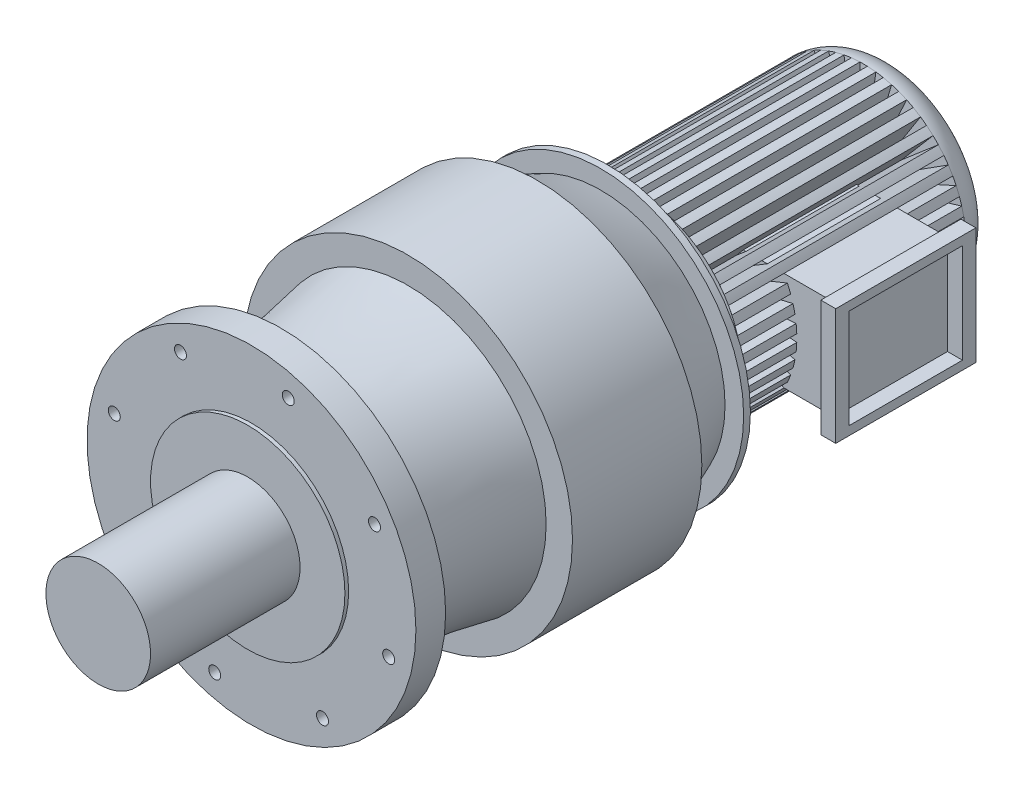
SolidWorks part; units mm, degrees
material "PBT Genel Kullanım"
ref_plane "Ön Düzlem" through (0, 0, 0) normal (0, 0, 1) x (1, 0, 0)
ref_plane "Üst Düzlem" through (0, 0, 0) normal (0, 1, 0) x (1, 0, 0)
ref_plane "Sağ Düzlem" through (0, 0, 0) normal (1, 0, 0) x (0, 0, -1)
sketch "Çizim1" plane through (0, 0, 0) normal (1, 0, 0) x (0, 0, -1)
  line L0 (0, 0) -> (0, 70)
  line L1 (0, 70) -> (200, 70)
  line L2 (200, 70) -> (200, 130)
  line L3 (244.7518, 220) -> (244.7518, 166.1344)
  line L4 (414.4471, 184.7501) -> (414.4471, 220)
  line L5 (200, 130) -> (205, 130)
  line L6 (205, 130) -> (205, 220)
  line L7 (205, 220) -> (244.7518, 220)
  line L8 (414.4471, 220) -> (459.3436, 220)
  line L9 (459.3436, 220) -> (587.4629, 220)
  line L10 (587.4629, 220) -> (587.4629, 203.9807)
  line L11 (0, 0) -> (1063.8815, 0) construction
  line L12 (672.3685, 166.1344) -> (672.3685, 191.0474)
  line L13 (672.3685, 191.0474) -> (681.4104, 191.0474)
  line L14 (681.4104, 118.9552) -> (723.8815, 118.9552)
  line L15 (723.8815, 118.9552) -> (723.8815, 136.4076)
  line L16 (681.4104, 191.0474) -> (681.4104, 118.9552)
  line L17 (723.8815, 136.4076) -> (1023.8815, 136.4076)
  line L18 (1063.8815, 96.4076) -> (1063.8815, 0)
  arc A0 (244.7518, 166.1344) -> (414.4471, 184.7501) centre (244.7518, 948.8914) ccw
  arc A1 (1063.8815, 96.4076) -> (1023.8815, 136.4076) centre (1023.8815, 96.4076) ccw
  arc A2 (587.4629, 203.9807) -> (672.3685, 166.1344) centre (948.0374, 898.7428) ccw
  dimension "D4" = 40
  dimension "D1" = 70
  dimension "D2" = 205
  dimension "D3" = 200
  dimension "D5" = 130
  dimension "D6" = 220
  dimension "D8" = 300
revolve "Döndür1" add sketch "Çizim1" angle 360 about L11 region at (0, 83.1407, -552.2359)
sketch "Çizim2" plane through (0, 0, -205) normal (0, 0, 1) x (1, 0, 0)
  line L0 (0, 0) -> (0, 243.7784) construction
  circle A1 centre (-95, 164.5448) radius 8
extrude "Kes-Ekstrüzyon4" cut sketch "Çizim2" against normal up to next contours A1 region at (-95, 164.5448, -205)
pattern_circular "Dairesel Çoğaltma1" count 8 over 360 of "Kes-Ekstrüzyon4"
ref_plane "Düzlem1" through (136.4076, 0, 0) normal (1, 0, 0) x (0, 0, -1)
sketch "Çizim4" plane through (136.4076, 0, 0) normal (1, 0, 0) x (0, 0, -1)
  line L1 (1023.8815, 136.4076) -> (1023.8815, -136.4076) construction
  line L2 (723.8815, 118.9552) -> (723.8815, -118.9552) construction
  line L3 (1023.8815, 0) -> (1023.8815, 5)
  line L4 (1023.8815, 5) -> (723.8815, 5)
  line L5 (723.8815, 5) -> (723.8815, 0)
  line L6 (1023.8815, -5) -> (723.8815, -5)
  line L7 (1023.8815, 0) -> (1023.8815, -5)
  line L8 (723.8815, 0) -> (723.8815, -5)
extrude "Kes-Ekstrüzyon5" cut sketch "Çizim4" against normal blind 80 draft 5
pattern_circular "Dairesel Çoğaltma2" count 40 over 360 of "Kes-Ekstrüzyon5"
sketch "Çizim5" plane through (136.4076, 0, 0) normal (1, 0, 0) x (0, 0, -1)
  line L0 (1023.8815, 0) -> (723.8815, 0) construction
  line L1 (798.1262, -66.3342) -> (949.6368, -66.3342)
  line L2 (798.1262, -66.3342) -> (798.1262, 66.3342)
  line L3 (798.1262, 66.3342) -> (949.6368, 66.3342)
  line L4 (949.6368, -66.3342) -> (949.6368, 66.3342)
  line L5 (798.1262, -66.3342) -> (949.6368, 66.3342) construction
  line L6 (798.1262, 66.3342) -> (949.6368, -66.3342) construction
  line L7 (1023.8735, 66.3342) -> (723.8895, 66.3342) construction
  line L9 (780.1567, -78.0156) -> (967.6063, -78.0156)
  line L10 (780.1567, -78.0156) -> (780.1567, 78.0156)
  line L11 (780.1567, 78.0156) -> (967.6063, 78.0156)
  line L12 (967.6063, -78.0156) -> (967.6063, 78.0156)
  line L13 (780.1567, -78.0156) -> (967.6063, 78.0156) construction
  line L14 (780.1567, 78.0156) -> (967.6063, -78.0156) construction
  point P0 (873.8815, 0)
  point P9 (873.8815, 0)
extrude "Yükseklik-Ekstrüzyon1" add sketch "Çizim5" against normal blind 80 and the other way blind 50 contours L1 L4 L3 L2 region at (136.4076, 0, -873.8815)
extrude "Yükseklik-Ekstrüzyon3" add sketch "Çizim5<3>" along normal blind 20 from offset 50 separate body
sketch "Çizim5<3>" plane through (136.4076, 0, 0) normal (1, 0, 0) x (0, 0, -1) same geometry as "Çizim5"
